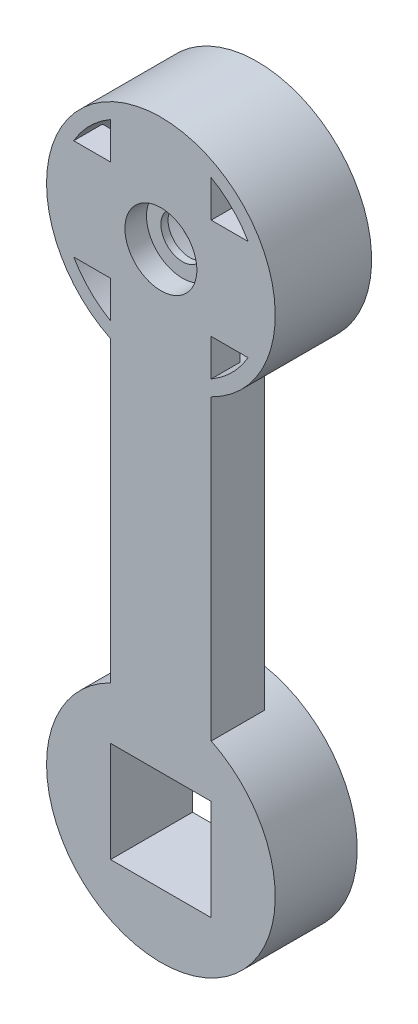
SolidWorks part; units mm, degrees
ref_plane "Front Plane" through (0, 0, 0) normal (0, 0, 1) x (1, 0, 0)
ref_plane "Top Plane" through (0, 0, 0) normal (0, 1, 0) x (1, 0, 0)
ref_plane "Right Plane" through (0, 0, 0) normal (1, 0, 0) x (0, 0, -1)
sketch "Sketch1" plane through (0, 0, 0) normal (0, 0, 1) x (1, 0, 0)
  line L5 (0, -17.5) -> (12.7696, -17.5) construction
  line L26 (0, 0) -> (0, -35) construction
  line L32 (0, 3.5) -> (7.1381, 3.5)
  line L33 (7.1381, 3.5) -> (-7.1381, 3.5)
  line L34 (0, -3.5) -> (7.1381, -3.5)
  line L35 (7.1381, -3.5) -> (-7.1381, -3.5)
  line L36 (3.5, -35) -> (3.5, -41.0622)
  line L37 (-3.5, -35) -> (-3.5, -41.0622)
  line L38 (-3.5, 0) -> (-3.5, 6.0622)
  line L45 (-3.5, 0) -> (-3.5, -35)
  line L47 (3.5, 0) -> (3.5, -35)
  line L48 (3.5, 0) -> (3.5, 6.0622)
  line L49 (7.1381, -31.5) -> (-7.1381, -31.5)
  line L50 (0, -31.5) -> (7.1381, -31.5)
  line L51 (7.1381, -38.5) -> (-7.1381, -38.5)
  line L52 (0, -38.5) -> (7.1381, -38.5)
  circle A0 centre (0, 0) radius 7.95
  circle A1 centre (0, 0) radius 3.5
  circle A2 centre (0, 0) radius 7
  circle A6 centre (0, 0) radius 1.5
  circle A11 centre (0, -35) radius 1.5
  circle A12 centre (0, -35) radius 7
  circle A13 centre (0, -35) radius 3.5
  circle A14 centre (0, -35) radius 7.95
  point P20 (0, -35)
  point P34 (0, -35)
  point P42 (0, 0)
  dimension "D1" = 15.9
  dimension "D2" = 7
  dimension "D6" = 14
  dimension "D9" = 3
  dimension "D3" = 7
  dimension "D7" = 35
extrude "Boss-Extrude4" add sketch "Sketch1" along normal blind 3 contours L48 A2 L38 L33 L32 | A2 L32 A0 L33 | L45 A14 L47 A0 | A14 L51 A12 | A12 L36 L51 L37 | A14 L49 A12 L51 | L36 A13 L51 | L51 A13 L37 | A14 L51 A12 L49 | A13 A11 | L45 A13 L49 | L49 A13 L47 | A12 L45 L49 L47 | A14 L49 A12 L45 | A14 L47 A12 L49 | A14 L45 A12 L47 | A12 L51 L37 L45 L49 | A12 L50 L47 L36 L52 | L45 A2 L47 L34 L35 | A2 L45 A0 L47 | A2 L47 A0 L34 | A2 L34 A0 L32 | A2 L33 A0 L35 | A2 L35 A0 L45 | L33 A2 L35 L45 L38 | L35 A2 L33 L48 L47 | A1 L34 L47 | A1 A6 | A1 L45 L35 | A1 L33 L38 | A1 L48 L32 region at (0, 5.1101, 0) region at (-2.7182, 2.7182, 0) region at (2.7182, 2.7182, 0) region at (2.4049, 2.4049, 0) region at (5.1101, 0, 0) region at (-5.1101, 0, 0) region at (2.7182, -2.7182, 0) region at (-2.7182, -2.7182, 0) region at (5.0555, 5.0555, 0) region at (7.1812, 0, 0) region at (-7.1812, 0, 0) region at (0, -5.1101, 0) region at (-5.2259, -5.2259, 0) region at (5.2259, -5.2259, 0) region at (0, -7.1812, 0) region at (0, -17.5, 0) region at (5.2259, -29.7741, 0) region at (0, -27.8188, 0) region at (-5.2259, -29.7741, 0) region at (0, -29.8899, 0) region at (7.1812, -35, 0) region at (-7.1812, -35, 0) region at (5.1101, -35, 0) region at (2.7182, -32.2818, 0) region at (-2.7182, -32.2818, 0) region at (-5.1101, -35, 0) region at (-6.6001, -38.6495, 0) region at (2.4049, -37.4049, 0) region at (2.7182, -37.7182, 0) region at (-2.7182, -37.7182, 0) region at (0, -40.1101, 0)
sketch "Sketch3" plane through (0, 0, 0) normal (0, 0, -1) x (-1, 0, 0)
  line L0 (-3.5, 6.0622) -> (-3.5, 3.5)
  line L1 (-3.5, 3.5) -> (-6.0622, 3.5)
  line L2 (-3.5, -6.0622) -> (-3.5, -3.5)
  line L3 (-3.5, -3.5) -> (-6.0622, -3.5)
  line L4 (3.5, -6.0622) -> (3.5, -3.5)
  line L5 (3.5, -3.5) -> (6.0622, -3.5)
  line L6 (3.5, 6.0622) -> (3.5, 3.5)
  line L7 (3.5, 3.5) -> (6.0622, 3.5)
  line L8 (0, 0) -> (0, -35) construction
  line L9 (0, -35) -> (0, -17.5) construction
  line L10 (0, -17.5) -> (14.5774, -17.5) construction
  line L11 (-3.5, 3.5) -> (-6.0622, 3.5)
  line L12 (-3.5, 6.0622) -> (-3.5, 3.5)
  line L13 (-3.5, -3.5) -> (-6.0622, -3.5)
  line L14 (-3.5, -6.0622) -> (-3.5, -3.5)
  line L15 (3.5, -3.5) -> (6.0622, -3.5)
  line L16 (3.5, -6.0622) -> (3.5, -3.5)
  line L17 (3.5, 3.5) -> (6.0622, 3.5)
  line L18 (3.5, 6.0622) -> (3.5, 3.5)
  line L19 (3.5, -41.0622) -> (3.5, -38.5)
  line L20 (3.5, -38.5) -> (6.0622, -38.5)
  line L21 (3.5, -28.9378) -> (3.5, -31.5)
  line L22 (3.5, -31.5) -> (6.0622, -31.5)
  line L23 (-3.5, -28.9378) -> (-3.5, -31.5)
  line L24 (-3.5, -31.5) -> (-6.0622, -31.5)
  line L25 (-3.5, -41.0622) -> (-3.5, -38.5)
  line L26 (-3.5, -38.5) -> (-6.0622, -38.5)
  line L27 (3.5, -38.5) -> (6.0622, -38.5)
  line L28 (3.5, -41.0622) -> (3.5, -38.5)
  line L29 (3.5, -31.5) -> (6.0622, -31.5)
  line L30 (3.5, -28.9378) -> (3.5, -31.5)
  line L31 (-3.5, -31.5) -> (-6.0622, -31.5)
  line L32 (-3.5, -28.9378) -> (-3.5, -31.5)
  line L33 (-3.5, -38.5) -> (-6.0622, -38.5)
  line L34 (-3.5, -41.0622) -> (-3.5, -38.5)
  circle A0 centre (0, 0) radius 1.5
  circle A1 centre (0, 0) radius 7.95
  circle A2 centre (0, 0) radius 7
  circle A3 centre (0, -35) radius 7
  circle A4 centre (0, -35) radius 7.95
  circle A5 centre (0, -35) radius 1.5
  line M2 (3.5, -38.5) -> (6.0622, -38.5)
  arc M3 (6.0622, -38.5) -> (3.5, -41.0622) centre (0, -35) cw
  line M4 (3.5, -41.0622) -> (3.5, -38.5)
  line M5 (-3.5, -38.5) -> (-3.5, -41.0622)
  arc M6 (-3.5, -41.0622) -> (-6.0622, -38.5) centre (0, -35) cw
  line M7 (-6.0622, -38.5) -> (-3.5, -38.5)
  arc M9 (3.5, -7.1381) -> (-3.5, -7.1381) centre (0, 0) ccw
  arc M11 (-3.5, -27.8619) -> (3.5, -27.8619) centre (0, -35) ccw
  line M12 (6.0622, -31.5) -> (3.5, -31.5)
  line M13 (3.5, -31.5) -> (3.5, -28.9378)
  arc M14 (3.5, -28.9378) -> (6.0622, -31.5) centre (0, -35) cw
  arc M15 (-3.5, -6.0622) -> (-6.0622, -3.5) centre (0, 0) cw
  line M16 (-6.0622, -3.5) -> (-3.5, -3.5)
  line M17 (-3.5, -3.5) -> (-3.5, -6.0622)
  line M18 (-3.5, -31.5) -> (-6.0622, -31.5)
  arc M19 (-6.0622, -31.5) -> (-3.5, -28.9378) centre (0, -35) cw
  line M20 (-3.5, -28.9378) -> (-3.5, -31.5)
  line M21 (3.5, -3.5) -> (6.0622, -3.5)
  arc M22 (6.0622, -3.5) -> (3.5, -6.0622) centre (0, 0) cw
  line M23 (3.5, -6.0622) -> (3.5, -3.5)
  line M24 (6.0622, 3.5) -> (3.5, 3.5)
  line M25 (3.5, 3.5) -> (3.5, 6.0622)
  arc M26 (3.5, 6.0622) -> (6.0622, 3.5) centre (0, 0) cw
  arc M27 (-6.0622, 3.5) -> (-3.5, 6.0622) centre (0, 0) cw
  line M28 (-3.5, 6.0622) -> (-3.5, 3.5)
  line M29 (-3.5, 3.5) -> (-6.0622, 3.5)
  circle M30 centre (0, 0) radius 1.5
  circle M31 centre (0, -35) radius 1.5
  dimension "D1" = 15.9
extrude "Boss-Extrude5" add sketch "Sketch3" along normal blind 3 contours A1 A2 M9 M26 M22 M15 M27 | A2 M25 M28 M29 M16 M17 M23 M21 M24 M30 | A3 M4 M2 M12 M13 M20 M18 M7 M5 M31 | A4 A3 M11 M3 M6 M19 M14 region at (0, 6.802, 0) region at (0, -41.802, 0) region at (-6.5556, -4.0868, 0) region at (4.0868, -41.5556, 0)
sketch "Sketch4" plane through (0, 0, 3) normal (0, 0, 1) x (1, 0, 0)
  line L0 (0, 0) -> (0, -35) construction
  line L1 (0, -35) -> (0, 0) construction
  line L2 (0, -17.5) -> (19.6941, -17.5) construction
  circle A1 centre (0, -35) radius 2.5
  circle A2 centre (0, 0) radius 2.5
  dimension "D2" = 5
extrude "Cut-Extrude1" cut sketch "Sketch4" against normal blind 1.5
sketch "Sketch5" plane through (0, 0, -3) normal (0, 0, -1) x (-1, 0, 0)
  circle A0 centre (0, 0) radius 7
extrude "Cut-Extrude2" cut sketch "Sketch5" against normal blind 4
sketch "Sketch6" plane through (0, 0, -3) normal (0, 0, -1) x (-1, 0, 0)
  circle A0 centre (0, -35) radius 7.95
extrude "Cut-Extrude3" cut sketch "Sketch6" against normal blind 1
sketch "Sketch7" plane through (0, 0, 1.5) normal (0, 0, 1) x (1, 0, 0)
  circle A0 centre (0, -35) radius 2.5
extrude "Cut-Extrude4" cut sketch "Sketch7" against normal blind 0.5
sketch "Sketch8" plane through (0, 0, -3) normal (0, 0, -1) x (-1, 0, 0)
  circle A0 centre (0, 0) radius 7.95
  circle A1 centre (0, 0) radius 7
extrude "Boss-Extrude6" add sketch "Sketch8" along normal blind 0.7
sketch "Sketch9" plane through (0, 0, -2) normal (0, 0, -1) x (-1, 0, 0)
  line L0 (-3.5, -28.9378) -> (-3.5, -31.5)
  line L1 (-3.5, -31.5) -> (-6.0622, -31.5)
  line L2 (-6.0622, -38.5) -> (-3.5, -38.5)
  line L3 (-3.5, -38.5) -> (-3.5, -41.0622)
  line L4 (6.0622, -38.5) -> (3.5, -38.5)
  line L5 (3.5, -38.5) -> (3.5, -41.0622)
  line L6 (3.5, -28.9378) -> (3.5, -31.5)
  line L7 (3.5, -31.5) -> (6.0622, -31.5)
  circle A0 centre (0, -35) radius 7.95
  circle A1 centre (0, -35) radius 7
  circle A2 centre (0, -35) radius 1.5
  line M1 (6.0622, -31.5) -> (3.5, -31.5)
  line M2 (3.5, -31.5) -> (3.5, -28.9378)
  arc M3 (3.5, -28.9378) -> (6.0622, -31.5) centre (0, -35) cw
  arc M4 (-3.5, -41.0622) -> (-6.0622, -38.5) centre (0, -35) cw
  line M5 (-6.0622, -38.5) -> (-3.5, -38.5)
  line M6 (-3.5, -38.5) -> (-3.5, -41.0622)
  arc M7 (6.0622, -38.5) -> (3.5, -41.0622) centre (0, -35) cw
  line M8 (3.5, -41.0622) -> (3.5, -38.5)
  line M9 (3.5, -38.5) -> (6.0622, -38.5)
  circle M10 centre (0, -35) radius 7.95
  line M11 (-3.5, -31.5) -> (-6.0622, -31.5)
  arc M12 (-6.0622, -31.5) -> (-3.5, -28.9378) centre (0, -35) cw
  line M13 (-3.5, -28.9378) -> (-3.5, -31.5)
  circle M14 centre (0, -35) radius 1.5
extrude "Boss-Extrude8" add sketch "Sketch9" along normal blind 0.7 contours A1 M2 M13 M11 M5 M6 M8 M9 M1 M14 | A1 M10 M3 M7 M4 M12 region at (0, -28.198, -2) region at (7.7251, -35, -2)
sketch "Sketch10" plane through (0, 0, 0) normal (0, 0, -1) x (-1, 0, 0)
  line L2 (-3.5, -7.1381) -> (-3.5, -27.8619)
  line L4 (3.5, -7.1381) -> (3.5, -27.8619)
  circle A0 centre (0, 0) radius 7.95
  circle A1 centre (0, -35) radius 7.95
  line M1 (-3.5, -7.1381) -> (-3.5, -27.8619)
  arc M2 (-3.5, -27.8619) -> (3.5, -27.8619) centre (0, -35) cw
  line M3 (3.5, -27.8619) -> (3.5, -7.1381)
  arc M4 (3.5, -7.1381) -> (-3.5, -7.1381) centre (0, 0) cw
extrude "Boss-Extrude9" add sketch "Sketch10" along normal blind 0.7 contours M4 M1 M2 M3 region at (0, -17.5, 0)
sketch "Sketch15" plane through (0, 0, -2.7) normal (0, 0, -1) x (-1, 0, 0)
  circle A0 centre (0, -35) radius 7
  circle A1 centre (0, -35) radius 4.9497
extrude "Boss-Extrude12" add sketch "Sketch15" against normal blind 5.7
sketch "Sketch16" plane through (0, 0, -2.7) normal (0, 0, -1) x (-1, 0, 0)
  line L1 (-3.5, -31.5) -> (3.5, -31.5)
  line L2 (-3.5, -31.5) -> (-3.5, -38.5)
  line L3 (-3.5, -38.5) -> (3.5, -38.5)
  line L4 (3.5, -31.5) -> (3.5, -38.5)
  line L5 (-3.5, -31.5) -> (3.5, -38.5) construction
  line L6 (-3.5, -38.5) -> (3.5, -31.5) construction
  point P0 (0, -35)
  dimension "D1" = 7
  dimension "D2" = 7
extrude "Cut-Extrude7" cut sketch "Sketch16" against normal blind 5.7
